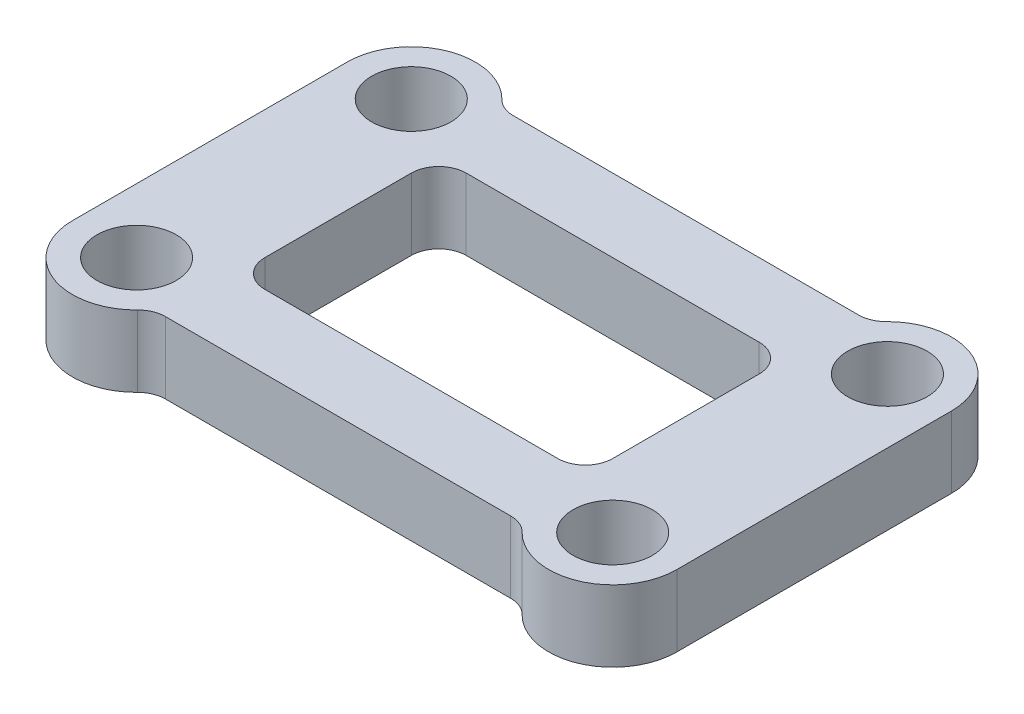
SolidWorks part; units mm, degrees
material "6061-T6 (SS)"
ref_plane "Front Plane" through (0, 0, 0) normal (0, 0, 1) x (1, 0, 0)
ref_plane "Top Plane" through (0, 0, 0) normal (0, 1, 0) x (1, 0, 0)
ref_plane "Right Plane" through (0, 0, 0) normal (1, 0, 0) x (0, 0, -1)
sketch "Sketch1" plane through (0, -19.05, 0) normal (0, -1, 0) x (1, 0, 0)
  line L0 (-29.21, 9.525) -> (-29.21, -9.525) construction
  line L5 (-24.765, 9.525) -> (-24.765, -9.525)
  line L6 (-33.655, 9.525) -> (-33.655, -9.525)
  line L7 (3.81, 9.525) -> (3.81, -9.525) construction
  line L8 (8.255, 9.525) -> (8.255, -9.525)
  line L9 (-0.635, 9.525) -> (-0.635, -9.525)
  arc A4 (-24.765, 9.525) -> (-33.655, 9.525) centre (-29.21, 9.525) ccw
  arc A5 (-33.655, -9.525) -> (-24.765, -9.525) centre (-29.21, -9.525) ccw
  arc A6 (8.255, 9.525) -> (-0.635, 9.525) centre (3.81, 9.525) ccw
  arc A7 (-0.635, -9.525) -> (8.255, -9.525) centre (3.81, -9.525) ccw
  point P2 (-29.21, 0)
  point P12 (3.81, 0)
  dimension "D1" = 4.445
  dimension "D2" = 4.445
extrude "Boss-Extrude2" add sketch "Sketch1" along normal blind 4.95
sketch "Sketch7" plane through (0, -24, 0) normal (0, -1, 0) x (1, 0, 0)
  line L0 (-29.21, 9.525) -> (3.81, 9.525)
  line L2 (-29.21, -9.525) -> (3.81, -9.525)
extrude "Extrude-Thin1" add sketch "Sketch7" against normal up to surface (4.95 mm away) thin up to face at (-29.21, -19.05, 0) thin type mid plane wall 5.08
hole_wizard "M5 Clearance Hole1" positions "3DSketch1" profile "Sketch5" hole size "M5" standard "ANSI Metric" end condition through all
sketch3d "3DSketch1"
  line L0 (-29.21, -24, 9.525) -> (-29.21, -19.05, 9.525) construction
  line L1 (-29.21, -24, -9.525) -> (-29.21, -19.05, -9.525) construction
  line L2 (3.81, -24, 9.525) -> (3.81, -19.05, 9.525) construction
  line L3 (3.81, -24, -9.525) -> (3.81, -19.05, -9.525) construction
  point P0 (-29.21, -24, 9.525)
  point P4 (-29.21, -24, -9.525)
  point P8 (3.81, -24, 9.525)
  point P12 (3.81, -24, -9.525)
sketch "Sketch5" plane through (-29.21, -24, 9.525) normal (1, 0, 0) x (0, 0, -1)
  line L0 (0, 0) -> (0, 4.95)
  line L1 (0, 4.95) -> (2.75, 4.95)
  line L2 (2.75, 4.95) -> (2.75, 0)
  line L5 (2.75, 0) -> (0, 0)
  line L11 (0, -6.35) -> (0, 107.95) construction
  dimension "Thru Hole Dia." = 5.5
  dimension "Thru Hole Depth" = 4.95
fillet "Fillet1" radius 1.905 8 edges at (-25.5622, -21.525, -12.065) (0.1622, -21.525, -12.065) (-0.635, -21.525, -6.985) (-24.765, -21.525, 6.985) (0.1622, -21.525, 12.065) (-25.5622, -21.525, 12.065) (-0.635, -21.525, 6.985) (-24.765, -21.525, -6.985)
